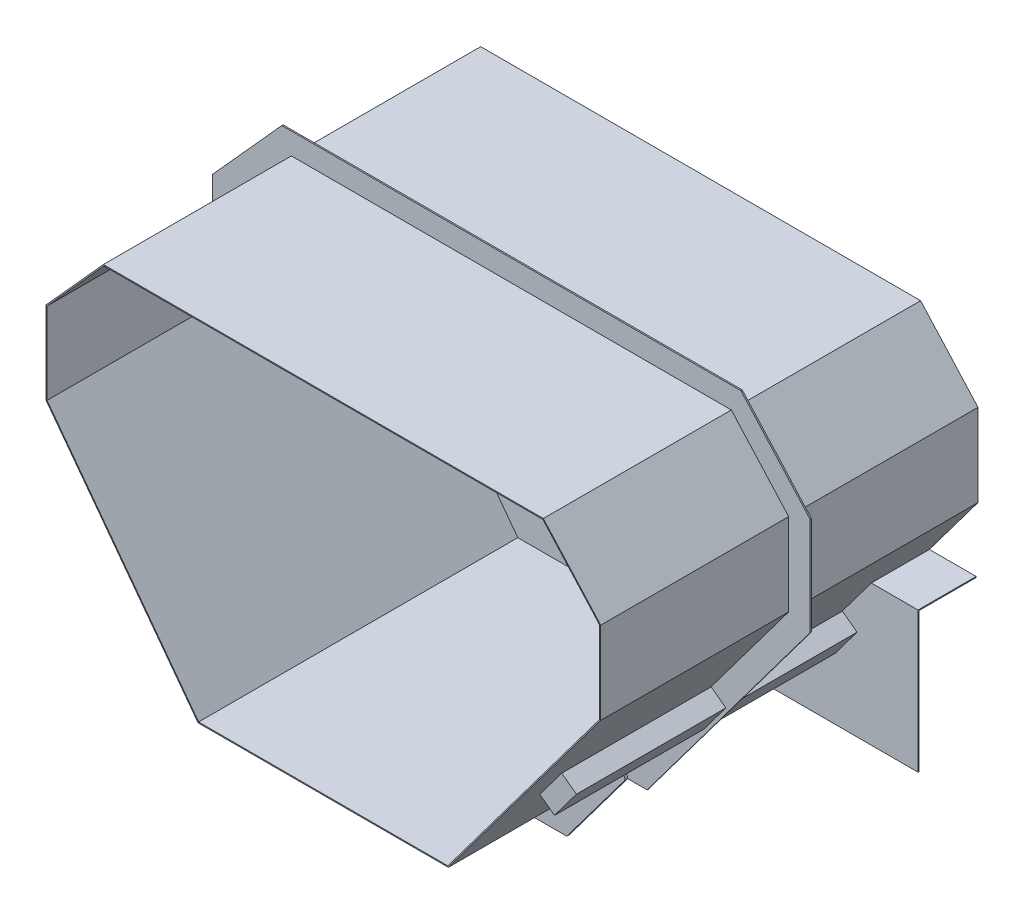
SolidWorks part; units mm, degrees
note: The reader was unsure of these and kept them because the rebuilt part matched: shared geometry of "Sketch1<4>".
ref_plane "Front Plane" through (0, 0, 0) normal (0, 0, 1) x (1, 0, 0)
ref_plane "Top Plane" through (0, 0, 0) normal (0, 1, 0) x (1, 0, 0)
ref_plane "Right Plane" through (0, 0, 0) normal (1, 0, 0) x (0, 0, -1)
sketch "Sketch1" plane through (0, 0, 0) normal (0, 0, 1) x (1, 0, 0)
  line L0 (-3854.0177, 0) -> (3226.6195, 0) construction
  line L1 (0, -2638.3658) -> (0, 2349.0088) construction
  line L2 (-1685, 804) -> (1685, 804)
  line L3 (-2124.5, 316) -> (-2124.5, -316)
  line L4 (2124.5, 316) -> (2124.5, -316)
  line L5 (-959.5, -1874) -> (957.5, -1874)
  line L6 (-959.5, -1874) -> (-2124.5, -316)
  line L7 (957.5, -1874) -> (2124.5, -316)
  line L8 (2124.5, 316) -> (1685, 804)
  line L9 (-1685, 804) -> (-2124.5, 316)
  line L10 (-1758.4512, 969) -> (1758.4512, 969)
  line L11 (2289.5, 379.3486) -> (1758.4512, 969)
  line L12 (2289.5, 379.3486) -> (2289.5, -370.9435)
  line L13 (1040.0636, -2039) -> (2289.5, -370.9435)
  line L14 (-1042.1485, -2039) -> (1040.0636, -2039)
  line L15 (-1042.1485, -2039) -> (-2289.5, -370.8681)
  line L16 (-2289.5, 379.3486) -> (-2289.5, -370.8681)
  line L17 (-1758.4512, 969) -> (-2289.5, 379.3486)
  line L18 (-1681.4387, 796) -> (1681.4387, 796)
  line L19 (-975.8062, -869.7801) -> (-2276.9211, -1842.6934) construction
  line L20 (2116.5, 312.9286) -> (1681.4387, 796)
  line L21 (2116.5, 312.9286) -> (2116.5, -313.3361)
  line L22 (953.4969, -1866) -> (2116.5, -313.3361)
  line L23 (-955.4928, -1866) -> (953.4969, -1866)
  line L24 (-955.4928, -1866) -> (-2116.5, -313.3397)
  line L25 (-2116.5, 312.9286) -> (-2116.5, -313.3397)
  line L26 (-1681.4387, 796) -> (-2116.5, 312.9286)
  line L27 (1022.9082, -905.9593) -> (1958.6592, -1606.8717) construction
  line L28 (-1642.926, -1193.8099) -> (-1475.2486, -1418.0515)
  line L29 (-1530.8053, -1109.9712) -> (-1642.926, -1193.8099)
  line L30 (-1475.2486, -1418.0515) -> (-1363.1278, -1334.2127)
  dimension "D1" = 3370
  dimension "D2" = 1685
  dimension "D3" = 4249
  dimension "D4" = 2124.5
  dimension "D5" = 632
  dimension "D6" = 316
  dimension "D7" = 632
  dimension "D8" = 316
  dimension "D9" = 488
  dimension "D10" = 439.5
  dimension "D11" = 488
  dimension "D12" = 439.5
  dimension "D13" = 1558
  dimension "D14" = 1165
  dimension "D15" = 1917
  dimension "D16" = 1167
  dimension "D17" = 1558
  dimension "D18" = 2678
  dimension "D19" = 165
  dimension "D20" = 8
  dimension "D21" = 90
  dimension "D22" = 810
  dimension "D23" = 90
  dimension "D24" = 810
  dimension "D25" = 140
  dimension "D26" = 280
  dimension "D27" = 140
extrude "Boss-Extrude1" add sketch "Sketch1" along normal mid plane 2890 contours L2 L9 L3 L6 L5 L7 L4 L8 L26 L18 L20 L21 L22 L23 L24 L25
extrude "Boss-Extrude2" add sketch "Sketch1<4>" along normal mid plane 10 contours L10 L17 L16 L15 L14 L13 L12 L11 L9 L2 L8 L4 L7 L5 L6 L3
sketch "Sketch1<4>" plane through (0, 0, 0) normal (0, 0, 1) x (1, 0, 0) same geometry as "Sketch1"
ref_plane "Plane1" through (-1475.2486, -1418.0515, 5) normal (0.5988, -0.8009, 0) x (-0.8009, -0.5988, 0)
sketch "Sketch4" plane through (0, 0, 5) normal (0, 0, 1) x (1, 0, 0)
  line L0 (0, 0) -> (0, -2747.8561) construction
  line L1 (-959.5, -1874) -> (-2124.5, -316) construction
  line L2 (-1642.926, -1193.8099) -> (-1475.2486, -1418.0515)
  line L3 (-1519.2961, -1450.9881) -> (-1431.2012, -1385.1148) construction
  line L4 (-1642.926, -1193.8099) -> (-1475.2486, -1418.0515) construction
  line L5 (-1475.2486, -1418.0515) -> (-1363.1278, -1334.2127)
  line L6 (-1363.1278, -1334.2127) -> (-1530.8053, -1109.9712)
  line L7 (-1530.8053, -1109.9712) -> (-1642.926, -1193.8099) construction
  line L8 (-1530.8053, -1109.9712) -> (-1642.926, -1193.8099)
  line L9 (1475.2486, -1418.0515) -> (1363.1278, -1334.2127)
  line L10 (1530.8053, -1109.9712) -> (1642.926, -1193.8099)
  line L11 (1363.1278, -1334.2127) -> (1530.8053, -1109.9712)
  line L12 (1642.926, -1193.8099) -> (1475.2486, -1418.0515)
  line L14 (-10, -1874.133) -> (10, -1874.133)
  line L15 (-10, -1874.133) -> (-10, -2024.133)
  line L16 (-10, -2024.133) -> (10, -2024.133)
  line L17 (10, -1874.133) -> (10, -2024.133)
  dimension "D1" = 10
  dimension "D2" = 20
  dimension "D3" = 150
extrude "Boss-Extrude4" add sketch "Sketch4" along normal mid plane 2290
sketch "Sketch5" plane through (0, 0, 0) normal (0, 0, 1) x (1, 0, 0)
  line L0 (-1363.1278, -1334.2127) -> (-1475.2486, -1418.0515)
  line L1 (-1475.2486, -1418.0515) -> (-1363.1278, -1334.2127) construction
  line L2 (-959.5, -1874) -> (-2124.5, -316) construction
  line L3 (-1042.1485, -2039) -> (-2289.5, -370.8681) construction
  line L4 (-1480.299, -1453.0442) -> (-1042.1485, -2039)
  line L5 (-1042.1485, -2039) -> (1040.0636, -2039)
  line L6 (1040.0636, -2039) -> (1479.4324, -1452.4219)
  line L8 (1363.1278, -1334.2127) -> (1474.3944, -1417.4127)
  line L9 (1363.1278, -1334.2127) -> (957.5, -1874)
  line L10 (957.5, -1874) -> (-959.5, -1874)
  line L11 (-959.5, -1874) -> (-1363.1278, -1334.2127)
  arc A0 (-1480.299, -1453.0442) -> (-1475.2486, -1418.0515) centre (-1460.2774, -1438.073) cw
  arc A1 (1479.4324, -1452.4219) -> (1474.3944, -1417.4127) centre (1459.4232, -1437.4343) ccw
  point P19 (-1495.2702, -1433.0227)
  dimension "D1" = 25
  dimension "D2" = 25
extrude "Boss-Extrude9" add sketch "Sketch5" along normal blind 20 from offset 600
sketch "Sketch6" plane through (0, 0, 0) normal (0, 1, 0) x (1, 0, 0)
  line L0 (0, 0) -> (0, 2378.9347) construction
  line L2 (-1752.916, 1000) -> (1752.916, 1000)
  line L3 (-1752.916, 1000) -> (-1752.916, 2215.7075)
  line L4 (-1752.916, 2215.7075) -> (1752.916, 2215.7075)
  line L5 (1752.916, 1000) -> (1752.916, 2215.7075)
  line L6 (-1752.916, 1000) -> (1752.916, 2215.7075) construction
  line L7 (-1752.916, 2215.7075) -> (1752.916, 1000) construction
  point P2 (0, 1607.8538)
  dimension "D1" = 1000
extrude "Cut-Extrude1" cut sketch "Sketch6" against normal up to next
sketch "Sketch7" plane through (0, 0, 0) normal (1, 0, 0) x (0, 0, -1)
  line L0 (1000, -812.9338) -> (1000, -1889.0315)
  line L1 (1000, -1889.0315) -> (1008, -1889.0315)
  line L2 (1008, -1889.0315) -> (1008, -820.9338)
  line L3 (1008, -820.9338) -> (1445.07, -820.9338)
  line L4 (1445.07, -820.9338) -> (1445.07, -812.9338)
  line L5 (1445.07, -812.9338) -> (1000, -812.9338)
  line L6 (1445, -812.9338) -> (1000, -812.9338) construction
  line L7 (1000, -812.0821) -> (1000, -1874) construction
  dimension "D1" = 8
  dimension "D2" = 8
extrude "Boss-Extrude11" add sketch "Sketch7" along normal mid plane 4220 separate body
sketch "Sketch8" plane through (-1646.3086, -1231.0331, 0) normal (-0.8009, -0.5988, 0) x (0, 0, 1)
  line L0 (-1000, -2776.4241) -> (-1000, -249.2858) construction
  line L1 (-80, -506.6219) -> (130, -506.6219)
  line L2 (-80, -506.6219) -> (-80, -776.6219)
  line L3 (-80, -776.6219) -> (130, -776.6219)
  line L4 (130, -506.6219) -> (130, -776.6219)
  line L5 (180, -506.6219) -> (390, -506.6219)
  line L6 (180, -506.6219) -> (180, -776.6219)
  line L7 (180, -776.6219) -> (390, -776.6219)
  line L8 (390, -506.6219) -> (390, -776.6219)
  line L9 (-130, -506.6219) -> (-340, -506.6219)
  line L10 (-130, -506.6219) -> (-130, -776.6219)
  line L11 (-130, -776.6219) -> (-340, -776.6219)
  line L12 (-340, -506.6219) -> (-340, -776.6219)
  line L13 (-390, -506.6219) -> (-850, -506.6219)
  line L14 (-390, -506.6219) -> (-390, -776.6219)
  line L15 (-390, -776.6219) -> (-850, -776.6219)
  line L16 (-850, -506.6219) -> (-850, -776.6219)
  line L18 (-787.3541, -565.0449) -> (-427.3541, -565.0449)
  line L19 (-787.3541, -565.0449) -> (-787.3541, -675.0449)
  line L20 (-787.3541, -675.0449) -> (-427.3541, -675.0449)
  line L21 (-427.3541, -565.0449) -> (-427.3541, -675.0449)
  line L22 (-290.3034, -565.0449) -> (-180.3034, -565.0449)
  line L23 (-290.3034, -565.0449) -> (-290.3034, -735.0449)
  line L24 (-290.3034, -735.0449) -> (-180.3034, -735.0449)
  line L25 (-180.3034, -565.0449) -> (-180.3034, -735.0449)
  line L26 (-27.196, -565.0449) -> (82.804, -565.0449)
  line L27 (-27.196, -565.0449) -> (-27.196, -735.0449)
  line L28 (-27.196, -735.0449) -> (82.804, -735.0449)
  line L29 (82.804, -565.0449) -> (82.804, -735.0449)
  line L30 (230, -556.6219) -> (340, -556.6219)
  line L31 (230, -556.6219) -> (230, -726.6219)
  line L32 (230, -726.6219) -> (340, -726.6219)
  line L33 (340, -556.6219) -> (340, -726.6219)
  point P34 (285, -556.6219)
  dimension "D1" = 210
  dimension "D2" = 270
  dimension "D3" = 210
  dimension "D4" = 210
  dimension "D5" = 460
  dimension "D6" = 150
  dimension "D7" = 50
  dimension "D8" = 50
  dimension "D9" = 50
  dimension "D10" = 170
  dimension "D11" = 110
  dimension "D12" = 110
  dimension "D13" = 170
  dimension "D14" = 110
  dimension "D15" = 170
  dimension "D16" = 360
  dimension "D17" = 110
  dimension "D18" = 50
  dimension "D19" = 50
extrude "Boss-Extrude12" add sketch "Sketch8" along normal blind 5
